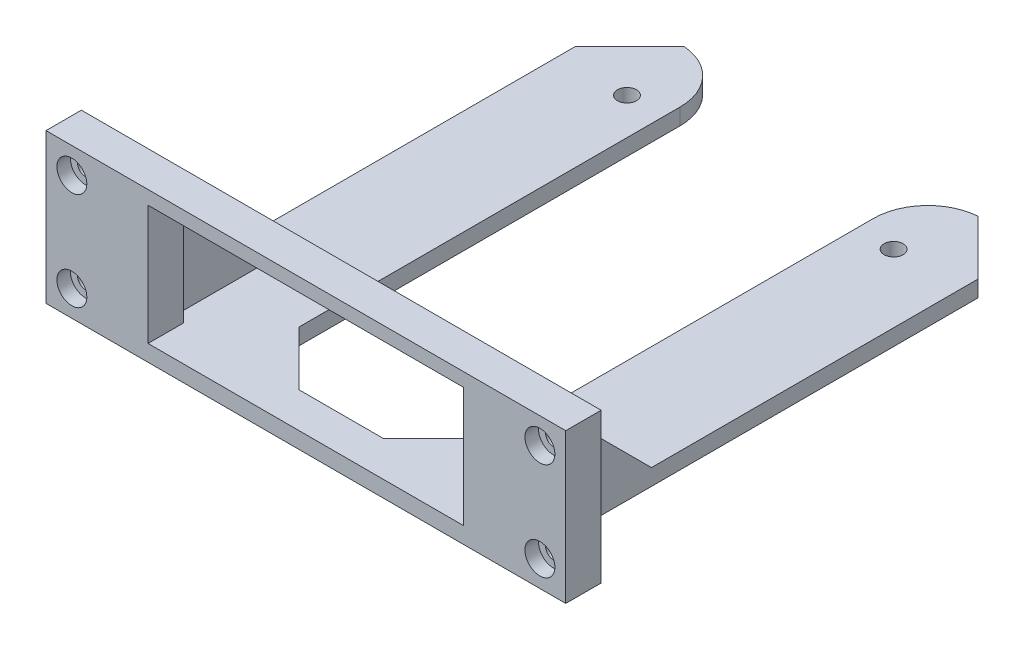
SolidWorks part; units mm, degrees
ref_plane "Front Plane" through (0, 0, 0) normal (0, 0, 1) x (1, 0, 0)
ref_plane "Top Plane" through (0, 0, 0) normal (0, 1, 0) x (1, 0, 0)
ref_plane "Right Plane" through (0, 0, 0) normal (1, 0, 0) x (0, 0, -1)
sketch "Sketch1" plane through (0, 0, 0) normal (0, 0, 1) x (1, 0, 0)
  line L1 (-47.75, 13.75) -> (47.75, 13.75)
  line L2 (-47.75, 13.75) -> (-47.75, -13.75)
  line L3 (-47.75, -13.75) -> (47.75, -13.75)
  line L4 (47.75, 13.75) -> (47.75, -13.75)
  line L5 (-47.75, 13.75) -> (47.75, -13.75) construction
  line L6 (-47.75, -13.75) -> (47.75, 13.75) construction
  point P0 (0, 0)
  dimension "D1" = 95.5
  dimension "D2" = 27.5
extrude "Boss-Extrude1" add sketch "Sketch1" along normal blind 6.5
sketch "Sketch2" plane through (0, 0, 0) normal (0, 0, -1) x (-1, 0, 0)
  line L0 (47.75, -13.75) -> (-47.75, -13.75) construction
  line L1 (-37, -13.75) -> (37, -13.75)
  line L2 (-37, -13.75) -> (-37, -10.75)
  line L3 (-37, -10.75) -> (37, -10.75)
  line L4 (37, -13.75) -> (37, -10.75)
  point P6 (0, -10.75)
  dimension "D1" = 74
  dimension "D2" = 3
extrude "Boss-Extrude2" add sketch "Sketch2" along normal blind 90
sketch "Sketch3" plane through (0, 0, 0) normal (0, 0, -1) x (-1, 0, 0)
  line L0 (37, -10.75) -> (-37, -10.75) construction
  line L1 (-29, -10.75) -> (29, -10.75)
  line L2 (-29, -10.75) -> (-29, 11.25)
  line L3 (-29, 11.25) -> (29, 11.25)
  line L4 (29, -10.75) -> (29, 11.25)
  point P6 (0, 11.25)
  dimension "D1" = 58
  dimension "D2" = 22
extrude "Cut-Extrude1" cut sketch "Sketch3" against normal blind 90
sketch "Sketch6" plane through (0, 0, 6.5) normal (0, 0, 1) x (1, 0, 0)
  line L0 (-47.75, -13.75) -> (47.75, -13.75) construction
  line L1 (47.75, 13.75) -> (-47.75, 13.75) construction
  line L2 (-47.75, 13.75) -> (-47.75, -13.75) construction
  line L3 (47.75, -13.75) -> (47.75, 13.75) construction
  point P0 (-43, 9)
  point P2 (-43, -9)
  point P4 (43, 9)
  point P6 (43, -9)
  dimension "D1" = 4.75
  dimension "D2" = 4.75
  dimension "D3" = 4.75
  dimension "D4" = 4.75
hole_wizard "CBORE for M2.5 SHCS1" positions "Sketch6" profile "Sketch5" counterbore size "M2.5" standard "ANSI Metric"
sketch "Sketch5" plane through (-43, 9, 6.5) normal (1, 0, 0) x (0, -1, 0)
  line L0 (0, 0) -> (0, 10.9712)
  line L1 (0, 10.9712) -> (1.45, 10.1)
  line L2 (1.45, 10.1) -> (1.45, 2.5)
  line L3 (1.45, 2.5) -> (2.75, 2.5)
  line L4 (2.75, 2.5) -> (2.75, 0)
  line L5 (2.75, 0) -> (0, 0)
  line L10 (0, 10.9712) -> (-1.45, 10.1) construction
  line L11 (0, -6.35) -> (0, 107.95) construction
  dimension "Hole Dia." = 2.9
  dimension "Hole Depth" = 10.1
  dimension "C'Bore Dia." = 5.5
  dimension "C'Bore Depth" = 2.5
  dimension "Drill Angle" = 118
sketch "Sketch7" plane through (0, 0, 0) normal (0, 0, -1) x (-1, 0, 0)
  line L0 (-29, 11.25) -> (-29, -10.75) construction
  line L9 (-37, -10.75) -> (-31, -10.75)
  line L10 (-37, -10.75) -> (-37, 9.25)
  line L11 (-37, 9.25) -> (-31, 9.25)
  line L12 (-31, -10.75) -> (-31, 9.25)
  line L13 (0, 15.125) -> (0, -15.125) construction
  line L14 (37, 9.25) -> (31, 9.25)
  line L15 (31, -10.75) -> (31, 9.25)
  line L16 (37, -10.75) -> (31, -10.75)
  line L17 (37, -10.75) -> (37, 9.25)
  dimension "D1" = 2
  dimension "D2" = 20
extrude "Boss-Extrude3" add sketch "Sketch7" along normal blind 20
chamfer "Chamfer1" distance 20 angle 45 2 edges at (34, 9.25, -20) (-34, 9.25, -20)
sketch "Sketch10" plane through (0, -10.75, 0) normal (0, 1, 0) x (1, 0, 0)
  line L0 (-29, -6.5) -> (29, -6.5) construction
  line L1 (0, -15.125) -> (0, 15.125) construction
  point P0 (-24.5, 77)
  point P2 (24.5, 77)
  point P4 (-24.5, 19)
  point P6 (24.5, 19)
  dimension "D1" = 58
  dimension "D2" = 49
  dimension "D3" = 25.5
  dimension "D4" = 24.5
hole_wizard "Ø1.0 (3.5) Diameter Hole1" positions "Sketch10" profile "Sketch11" hole size "Ø1.0" standard "ANSI Metric"
sketch "Sketch11" plane through (-24.5, -10.75, -77) normal (1, 0, 0) x (0, 0, 1)
  line L0 (0, 0) -> (0, 11.1515)
  line L1 (0, 11.1515) -> (1.75, 10.1)
  line L2 (1.75, 10.1) -> (1.75, 0)
  line L5 (1.75, 0) -> (0, 0)
  line L10 (0, 11.1515) -> (-1.75, 10.1) construction
  line L11 (0, -6.35) -> (0, 107.95) construction
  dimension "Hole Dia." = 3.5
  dimension "Hole Depth" = 10.1
  dimension "Drill Angle" = 118
sketch "Sketch12" plane through (0, -10.75, 0) normal (0, 1, 0) x (1, 0, 0)
  line L0 (-37, 90) -> (37, 90) construction
  line L1 (-17.75, 90) -> (17.75, 90)
  line L2 (-17.75, 90) -> (-17.75, 0)
  line L3 (-17.75, 0) -> (17.75, 0)
  line L4 (17.75, 90) -> (17.75, 0)
  line L5 (47.75, 0) -> (-47.75, 0) construction
  circle A1 centre (-24.5, 77) radius 1.75 construction
  circle A2 centre (24.5, 77) radius 1.75 construction
  dimension "D1" = 5
  dimension "D2" = 5
extrude "Cut-Extrude2" cut sketch "Sketch12" against normal blind 20
chamfer "Chamfer2" distance 10 angle 45 4 edges at (-17.75, -12.25, 0) (17.75, -12.25, 0) (37, -12.25, -90) (-37, -12.25, -90)
fillet "Fillet1" radius 10 2 edges at (-17.75, -12.25, -90) (17.75, -12.25, -90)
